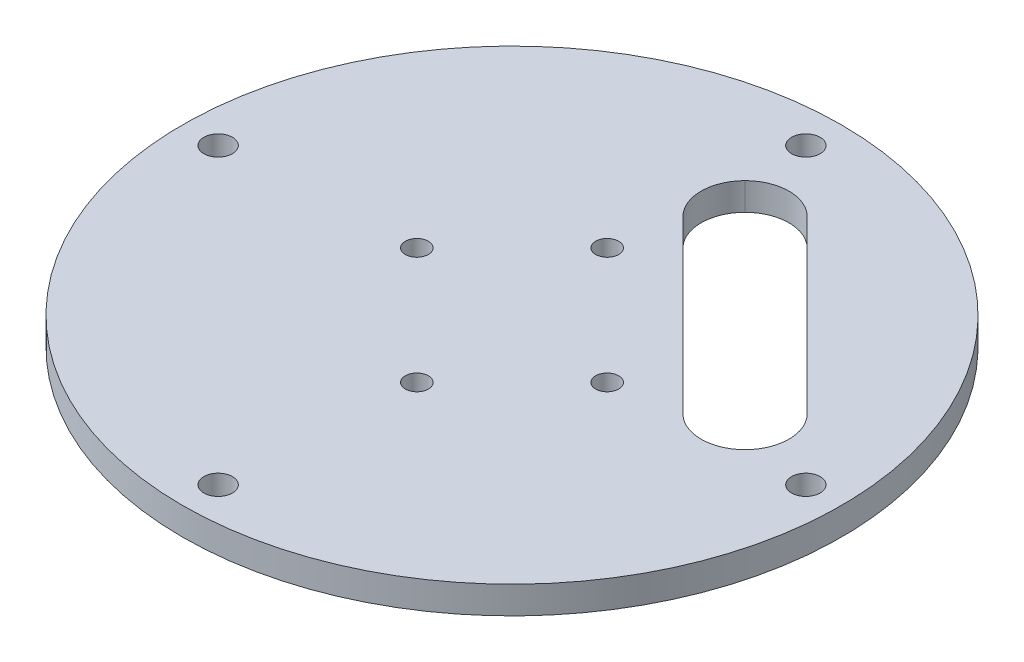
SolidWorks part; units mm, degrees
ref_plane "前视基准面" through (0, 0, 0) normal (0, 0, 1) x (1, 0, 0)
ref_plane "上视基准面" through (0, 0, 0) normal (0, 1, 0) x (1, 0, 0)
ref_plane "右视基准面" through (0, 0, 0) normal (1, 0, 0) x (0, 0, -1)
other "Configuration Table"
sketch "草图1" plane through (0, 0, 0) normal (0, 1, 0) x (1, 0, 0)
  line L0 (0, 0) -> (0, 60) construction
  line L1 (0, 0) -> (60, 0) construction
  line L2 (0, 0) -> (42.4264, 42.4264) construction
  line L3 (0, 0) -> (42.4264, -42.4264) construction
  line L4 (-5.6569, 36.7696) -> (36.7696, -5.6569)
  line L5 (-5.6569, 36.7696) -> (5.6569, 48.0833)
  line L6 (36.7696, -5.6569) -> (48.0833, 5.6569)
  line L7 (5.6569, 48.0833) -> (48.0833, 5.6569)
  circle A0 centre (0, 0) radius 60
  circle A1 centre (0, 53.5) radius 2.6
  circle A2 centre (53.5, 0) radius 2.6
  circle A3 centre (0, -53.5) radius 2.6
  circle A4 centre (-53.5, 0) radius 2.6
  circle A5 centre (-1.9445, 19.2687) radius 2.1
  circle A6 centre (19.2687, -1.9445) radius 2.1
  circle A7 centre (1.9445, -19.2687) radius 2.1
  circle A8 centre (-19.2687, 1.9445) radius 2.1
  point P16 (0, 0)
  point P19 (0, 0)
  point P20 (0, 0)
  point P23 (15.5563, 15.5563)
  point P24 (26.8701, 26.8701)
  point P32 (0, 0)
  point P33 (0, 0)
  point P34 (0, 0)
  dimension "D1" = 120
  dimension "D4" = 5.2
  dimension "D5" = 15
  dimension "D6" = 12.25
  dimension "D8" = 4.2
  dimension "D9" = 60
  dimension "D2" = 45
  dimension "D3" = 53.5
  dimension "D7" = 45
  dimension "D10" = 22
  dimension "D11" = 16
  dimension "D12" = 15
extrude "凸台-拉伸1" add sketch "草图1" along normal blind 5
fillet "圆角1" radius 8 4 edges at (36.7696, 2.5, 5.6569) (48.0833, 2.5, -5.6569) (5.6569, 2.5, -48.0833) (-5.6569, 2.5, -36.7696)
